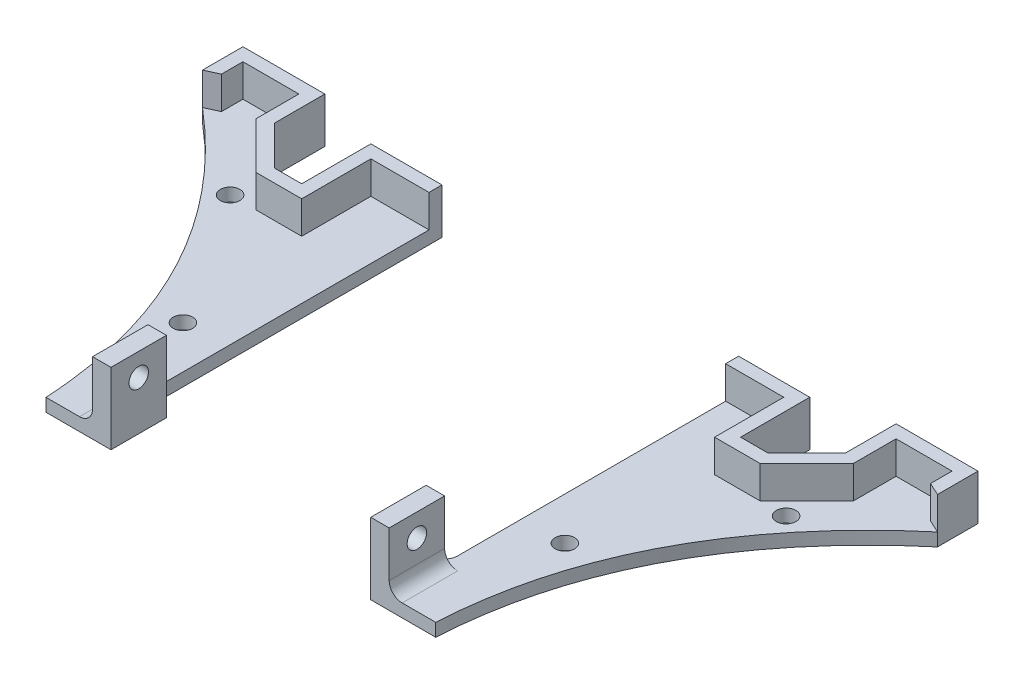
SolidWorks part; units mm, degrees
ref_plane "Front Plane" through (0, 0, 0) normal (0, 0, 1) x (1, 0, 0)
ref_plane "Top Plane" through (0, 0, 0) normal (0, 1, 0) x (1, 0, 0)
ref_plane "Right Plane" through (0, 0, 0) normal (1, 0, 0) x (0, 0, -1)
sketch "Sketch1" plane through (0, 0, 0) normal (0, 1, 0) x (1, 0, 0)
  line L0 (-56.5883, 22.2246) -> (-56.5883, 28.4551)
  line L1 (-22.8361, -28.4551) -> (-30, -28.4551)
  line L2 (-43.9759, 28.4551) -> (-56.5883, 28.4551)
  line L6 (-37.9759, 14.6993) -> (-33.7879, 14.6993)
  line L7 (-43.9759, 20.6993) -> (-37.9759, 14.6993)
  line L8 (-43.9759, 20.6993) -> (-43.9759, 28.4551)
  line L21 (-22.8361, -28.4551) -> (-22.8361, 25.3517)
  line L22 (-33.7879, 25.3517) -> (-22.8361, 25.3517)
  line L23 (-33.7879, 25.3517) -> (-33.7879, 14.6993)
  line L24 (0, -55) -> (0, 55) construction
  line L25 (33.7879, 25.3517) -> (33.7879, 14.6993)
  line L26 (33.7879, 25.3517) -> (22.8361, 25.3517)
  line L27 (22.8361, -28.4551) -> (22.8361, 25.3517)
  line L28 (43.9759, 20.6993) -> (43.9759, 28.4551)
  line L29 (43.9759, 20.6993) -> (37.9759, 14.6993)
  line L30 (37.9759, 14.6993) -> (33.7879, 14.6993)
  line L31 (43.9759, 28.4551) -> (56.5883, 28.4551)
  line L32 (22.8361, -28.4551) -> (30, -28.4551)
  line L33 (56.5883, 22.2246) -> (56.5883, 28.4551)
  parabola Q0 (30, -28.4551) -> (56.5883, 22.2246) focus (64.3146, -20.2927) apex (33.8007, -9.3631)
  parabola Q1 (-30, -28.4551) -> (-56.5883, 22.2246) focus (-64.3146, -20.2927) apex (-33.8007, -9.3631)
extrude "Boss-Extrude1" add sketch "Sketch1" along normal blind 2
sketch "Sketch2" plane through (0, 2, 0) normal (0, 1, 0) x (1, 0, 0)
  line L87 (-54.5883, 23.1453) -> (-56.5883, 22.2246)
  line L88 (-56.5883, 28.4551) -> (-56.5883, 22.2246) construction
  line L89 (-31.7879, 23.3517) -> (-22.8361, 23.3517)
  line L91 (-22.8361, 25.3517) -> (-33.7879, 25.3517) construction
  line L92 (-33.7879, 25.3517) -> (-33.7879, 14.6993) construction
  line L93 (-33.7879, 14.6993) -> (-37.9759, 14.6993) construction
  line L94 (-37.9759, 14.6993) -> (-43.9759, 20.6993) construction
  line L95 (-43.9759, 20.6993) -> (-43.9759, 28.4551) construction
  line L96 (-24.8361, 23.3517) -> (-31.7879, 23.3517)
  line L97 (-31.7879, 23.3517) -> (-31.7879, 12.6993)
  line L102 (-31.7879, 12.6993) -> (-38.8044, 12.6993)
  line L103 (-38.8044, 12.6993) -> (-45.9759, 19.8708)
  line L104 (-45.9759, 19.8708) -> (-45.9759, 26.4551)
  line L105 (-45.9759, 26.4551) -> (-54.5883, 26.4551)
  line L106 (-54.5883, 26.4551) -> (-54.5883, 23.1453)
  line L107 (-28.1314, -26.4551) -> (-24.8361, -26.4551)
  line L108 (-24.8361, -26.4551) -> (-24.8361, 23.3517)
  line L110 (-31.7879, 23.3517) -> (-31.7879, 12.6993)
  line L111 (-31.7879, 12.6993) -> (-38.8044, 12.6993)
  line L112 (-38.8044, 12.6993) -> (-45.9759, 19.8708)
  line L113 (-45.9759, 19.8708) -> (-45.9759, 26.4551)
  line L114 (-45.9759, 26.4551) -> (-54.5883, 26.4551)
  line L115 (-54.5883, 26.4551) -> (-54.5883, 23.1453)
  line L118 (-43.9759, 28.4551) -> (-56.5883, 28.4551) construction
  line L119 (-22.8361, 25.3517) -> (-33.7879, 25.3517)
  line L120 (-33.7879, 25.3517) -> (-33.7879, 14.6993)
  line L121 (-33.7879, 14.6993) -> (-37.9759, 14.6993)
  line L122 (-37.9759, 14.6993) -> (-43.9759, 20.6993)
  line L123 (-43.9759, 20.6993) -> (-43.9759, 28.4551)
  line L124 (-43.9759, 28.4551) -> (-56.5883, 28.4551)
  line L125 (-56.5883, 28.4551) -> (-56.5883, 22.2246)
  line L126 (-22.8361, -28.4551) -> (-22.8361, 25.3517) construction
  line L127 (-22.8361, 23.3517) -> (-22.8361, 25.3517)
  line L128 (0, -55) -> (0, 55) construction
  line L129 (22.8361, 23.3517) -> (22.8361, 25.3517)
  line L130 (56.5883, 28.4551) -> (56.5883, 22.2246)
  line L131 (43.9759, 28.4551) -> (56.5883, 28.4551)
  line L132 (43.9759, 20.6993) -> (43.9759, 28.4551)
  line L133 (37.9759, 14.6993) -> (43.9759, 20.6993)
  line L134 (33.7879, 14.6993) -> (37.9759, 14.6993)
  line L135 (33.7879, 25.3517) -> (33.7879, 14.6993)
  line L136 (22.8361, 25.3517) -> (33.7879, 25.3517)
  line L137 (54.5883, 26.4551) -> (54.5883, 23.1453)
  line L138 (45.9759, 26.4551) -> (54.5883, 26.4551)
  line L139 (45.9759, 19.8708) -> (45.9759, 26.4551)
  line L140 (38.8044, 12.6993) -> (45.9759, 19.8708)
  line L141 (31.7879, 12.6993) -> (38.8044, 12.6993)
  line L142 (31.7879, 23.3517) -> (31.7879, 12.6993)
  line L143 (31.7879, 23.3517) -> (22.8361, 23.3517)
  line L144 (54.5883, 23.1453) -> (56.5883, 22.2246)
  spline S0 degree 3 poles (355.549, 935.1677) (-543.6815, -23.2259) (-139.333, 126.3463) (-42.9049, 11.059) (-41.4488, 9.1514) (-39.4, 6.175) (-38.7396, 5.1636) (-37.4666, 3.1004) (-36.8533, 2.0468) (-33.9484, -3.2583) (-32.1105, -7.6699) (-30.0764, -14.5367) (-29.5188, -16.8672) (-28.8627, -20.425) (-28.674, -21.6221) (-7.5514, -182.2777) (-526.6137, -399.768) (895.9743, -408.5754) knots -7.464113 -7.464113 -7.464113 -7.464113 0.25 0.25 0.375 0.375 0.4375 0.4375 0.5 0.5 0.75 0.75 0.875 0.875 0.9375 0.9375 9.20233 9.20233 9.20233 9.20233 only from (-54.5883, 23.1453) to (-28.1314, -26.4551)
  dimension "D1" = 2
extrude "Boss-Extrude3" add sketch "Sketch2" along normal blind 5
sketch "Sketch3" plane through (0, 0, 0) normal (0, -1, 0) x (1, 0, 0)
  circle A0 centre (-29.4027, 7.9664) radius 1.5
  circle A1 centre (-42.8051, -12.6988) radius 1.5
  circle A2 centre (29.4027, 7.9664) radius 1.5
  circle A3 centre (42.8051, -12.6988) radius 1.5
extrude "Cut-Extrude1" cut sketch "Sketch3" against normal up to surface (2 mm away) up to face at (-40.8239, 2, -14.4257)
sketch "Sketch4" plane through (0, 2, 0) normal (0, 1, 0) x (1, 0, 0)
  line L0 (27.312, 18.6025) -> (27.312, 3.6025)
  line L1 (33.8053, 18.6025) -> (22.8327, 18.6025) construction
  line L3 (27.312, 3.6025) -> (22.8361, 3.6025)
  line L4 (22.8361, 23.3517) -> (22.8361, -28.4551) construction
  line L5 (22.8361, 3.6025) -> (22.8361, 18.6025)
  line L6 (22.8361, 18.6025) -> (27.312, 18.6025)
  dimension "D1" = 15
extrude "Cut-Extrude2" [suppressed] cut sketch "Sketch4" against normal up to surface (2 mm away) up to face at (29.4027, 0, 6.4664)
sketch "Sketch5" plane through (0, 0, 0) normal (0, 1, 0) x (1, 0, 0)
  line L0 (0, -3.85) -> (0, 3.85) construction
  line L1 (-22.8361, -28.4551) -> (-19.9961, -28.4551)
  line L2 (-22.8361, -28.4551) -> (-22.8361, -19.9151)
  line L3 (-22.8361, -19.9151) -> (-19.9961, -19.9151)
  line L4 (-19.9961, -28.4551) -> (-19.9961, -19.9151)
  line L5 (19.9961, -28.4551) -> (19.9961, -19.9151)
  line L6 (22.8361, -19.9151) -> (19.9961, -19.9151)
  line L7 (22.8361, -28.4551) -> (22.8361, -19.9151)
  line L8 (22.8361, -28.4551) -> (19.9961, -28.4551)
  dimension "D1" = 2.84
  dimension "D2" = 8.54
extrude "Boss-Extrude4" add sketch "Sketch5" along normal blind 11
fillet "Fillet1" radius 2 1 edges at (-22.8361, 2, 24.1851)
fillet "Fillet2" radius 2 1 edges at (-22.8361, 1, 19.9151)
fillet "Fillet3" radius 2 1 edges at (22.8361, 2, 24.1851)
fillet "Fillet4" radius 2 1 edges at (22.8361, 1, 19.9151)
sketch "Sketch6" plane through (22.8361, 0, 0) normal (1, 0, 0) x (0, 0, -1)
  line L0 (-24.1851, 11) -> (-24.1851, 4) construction
  line L1 (-28.4551, 11) -> (-19.9151, 11) construction
  line L2 (-28.4551, 4) -> (-19.9151, 4) construction
  circle A0 centre (-24.1851, 7.5) radius 1.5
  dimension "D1" = 3
extrude "Cut-Extrude3" cut sketch "Sketch6" against normal up to surface (45.6723 mm away) contours A0 up to face at (-22.8361, 7.5, 24.1851)
